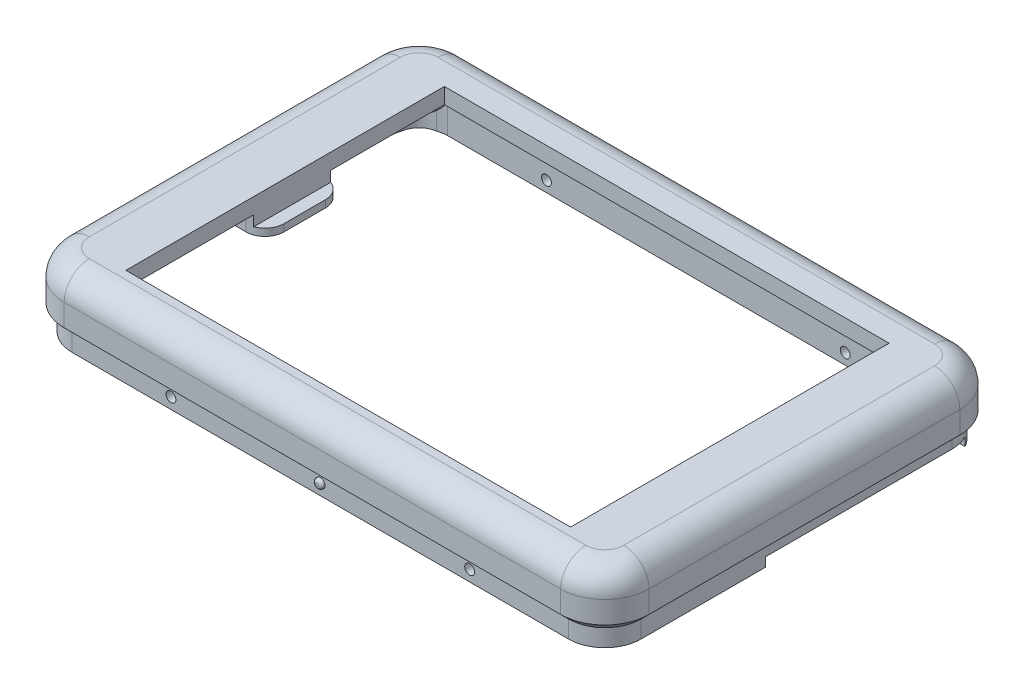
SolidWorks part; units mm, degrees
ref_plane "Front Plane" through (0, 0, 0) normal (0, 0, 1) x (1, 0, 0)
ref_plane "Top Plane" through (0, 0, 0) normal (0, 1, 0) x (1, 0, 0)
ref_plane "Right Plane" through (0, 0, 0) normal (1, 0, 0) x (0, 0, -1)
sketch "Sketch1" plane through (0, 0, 0) normal (0, 1, 0) x (1, 0, 0)
  line L0 (46.3567, -24.641) -> (46.3567, 24.641)
  line L1 (39.3567, 31.641) -> (-39.3567, 31.641)
  line L2 (-46.3567, 24.641) -> (-46.3567, -24.641)
  line L3 (-39.3567, -31.641) -> (39.3567, -31.641)
  arc A0 (46.3567, 24.641) -> (39.3567, 31.641) centre (39.3567, 24.641) ccw
  arc A1 (-39.3567, 31.641) -> (-46.3567, 24.641) centre (-39.3567, 24.641) ccw
  arc A2 (-46.3567, -24.641) -> (-39.3567, -31.641) centre (-39.3567, -24.641) ccw
  arc A3 (39.3567, -31.641) -> (46.3567, -24.641) centre (39.3567, -24.641) ccw
extrude "Boss-Extrude1" add sketch "Sketch1" along normal blind 4.5
shell "Shell1" thickness 2.5 removed face at (0, 0, 0)
sketch "Sketch2" plane through (0, 4.5, 0) normal (0, 1, 0) x (1, 0, 0)
  line L0 (39.3567, 31.641) -> (-39.3567, 31.641) construction
  line L1 (-34.8567, 24.141) -> (35.6433, 24.141)
  line L2 (-34.8567, 24.141) -> (-34.8567, -26.359)
  line L3 (-34.8567, -26.359) -> (35.6433, -26.359)
  line L4 (35.6433, 24.141) -> (35.6433, -26.359)
  line L6 (-43.8567, 24.641) -> (-43.8567, -24.641) construction
  dimension "D1" = 70.5
  dimension "D2" = 50.5
  dimension "D3" = 7.5
  dimension "D4" = 9
extrude "Cut-Extrude1" cut sketch "Sketch2" against normal blind 6
fillet "Fillet1" radius 2 8 edges at (42.5387, 2, 27.823) (0, 2, 29.141) (-42.5387, 2, 27.823) (-43.8567, 2, 0) (-42.5387, 2, -27.823) (0, 2, -29.141) (42.5387, 2, -27.823) (43.8567, 2, 0)
fillet "Fillet2" radius 4 8 edges at (-44.3064, 4.5, 29.5908) (-46.3567, 4.5, 0) (-44.3064, 4.5, -29.5908) (0, 4.5, -31.641) (44.3064, 4.5, -29.5908) (46.3567, 4.5, 0) (44.3064, 4.5, 29.5908) (0, 4.5, 31.641)
sketch "Sketch3" plane through (0, 2, 0) normal (0, -1, 0) x (1, 0, 0)
  circle A0 centre (-40.3931, 23.336) radius 1.25
  circle A1 centre (-40.3931, 23.336) radius 3.25
  circle A2 centre (-40.3931, -25.664) radius 1.25
  circle A3 centre (-40.3931, -25.664) radius 3.25
  circle A4 centre (37.6385, -25.664) radius 1.25
  circle A5 centre (37.6385, -25.664) radius 3.25
  circle A6 centre (37.6385, 23.336) radius 1.25
  circle A7 centre (37.6385, 23.336) radius 3.25
  dimension "D1" = 2
  dimension "D2" = 2
  dimension "D3" = 2
  dimension "D4" = 2
extrude "Boss-Extrude2" add sketch "Sketch3" along normal blind 2.5
sketch "Sketch4" plane through (0, 0, 0) normal (0, -1, 0) x (1, 0, 0)
  line L0 (39.3567, 29.141) -> (-39.3567, 29.141)
  line L1 (-43.8567, 24.641) -> (-43.8567, -24.641)
  line L2 (-39.3567, -29.141) -> (39.3567, -29.141)
  line L3 (43.8567, -24.641) -> (43.8567, 24.641)
  line L4 (39.3567, 31.641) -> (-39.3567, 31.641)
  line L5 (-46.3567, 24.641) -> (-46.3567, -24.641)
  line L6 (-39.3567, -31.641) -> (39.3567, -31.641)
  line L7 (46.3567, -24.641) -> (46.3567, 24.641)
  line L8 (39.3567, 31.641) -> (-39.3567, 31.641)
  line L9 (-46.3567, 24.641) -> (-46.3567, -24.641)
  line L10 (-39.3567, -31.641) -> (39.3567, -31.641)
  line L11 (46.3567, -24.641) -> (46.3567, 24.641)
  arc A0 (-39.3567, 29.141) -> (-43.8567, 24.641) centre (-39.3567, 24.641) ccw
  arc A1 (-43.8567, -24.641) -> (-39.3567, -29.141) centre (-39.3567, -24.641) ccw
  arc A2 (39.3567, -29.141) -> (43.8567, -24.641) centre (39.3567, -24.641) ccw
  arc A3 (43.8567, 24.641) -> (39.3567, 29.141) centre (39.3567, 24.641) ccw
  arc A4 (46.3567, 24.641) -> (39.3567, 31.641) centre (39.3567, 24.641) ccw
  arc A5 (-39.3567, 31.641) -> (-46.3567, 24.641) centre (-39.3567, 24.641) ccw
  arc A6 (-46.3567, -24.641) -> (-39.3567, -31.641) centre (-39.3567, -24.641) ccw
  arc A7 (39.3567, -31.641) -> (46.3567, -24.641) centre (39.3567, -24.641) ccw
  arc A8 (46.3567, 24.641) -> (39.3567, 31.641) centre (39.3567, 24.641) ccw
  arc A9 (-39.3567, 31.641) -> (-46.3567, 24.641) centre (-39.3567, 24.641) ccw
  arc A10 (-46.3567, -24.641) -> (-39.3567, -31.641) centre (-39.3567, -24.641) ccw
  arc A11 (39.3567, -31.641) -> (46.3567, -24.641) centre (39.3567, -24.641) ccw
  dimension "D1" = 0
  dimension "D2" = 2.5
extrude "Boss-Extrude3" add sketch "Sketch4" along normal blind 3
sketch "Sketch5" plane through (-34.8567, 0, 0) normal (1, 0, 0) x (0, 0, -1)
  line L1 (-6.2748, 0.3532) -> (6.2927, 0.3532)
  line L2 (-6.2748, 0.3532) -> (-6.2748, 2)
  line L3 (-6.2748, 2) -> (6.2927, 2)
  line L4 (6.2927, 0.3532) -> (6.2927, 2)
extrude "Boss-Extrude4" add sketch "Sketch5" against normal blind 4
sketch "Sketch6" plane through (0, 0, 6.2748) normal (0, 0, 1) x (1, 0, 0)
  line L0 (-34.8567, 0.3532) -> (-32.8849, 0.3532)
  line L1 (-32.8849, 0.3532) -> (-32.8849, -0.7856)
  line L2 (-32.8849, -0.7856) -> (-38.3084, -0.7856)
  line L3 (-38.3084, -0.7856) -> (-38.8567, 0.3532)
  line L4 (-38.8567, 0.3532) -> (-34.8567, 0.3532)
extrude "Boss-Extrude5" add sketch "Sketch6" against normal up to surface (12.5674 mm away) up to face at (-36.8567, 1.1766, -6.2927)
fillet "Fillet4" radius 3 2 edges at (-32.8849, -0.2162, -6.2927) (-32.8849, -0.2162, 6.2748)
sketch "Sketch8" plane through (0, 4.5, 0) normal (0, 1, 0) x (1, 0, 0)
  line L1 (-34.8567, 24.141) -> (35.6433, 24.141)
  line L2 (-34.8567, 24.141) -> (-34.8567, -26.359)
  line L3 (-34.8567, -26.359) -> (35.6433, -26.359)
  line L4 (35.6433, 24.141) -> (35.6433, -26.359)
extrude "Cut-Extrude2" cut sketch "Sketch8" against normal blind 4
sketch "Sketch10" plane through (0, -3, 0) normal (0, -1, 0) x (1, 0, 0)
  line L4 (-39.3567, -29.141) -> (39.3567, -29.141) construction
  line L5 (43.8567, -24.641) -> (43.8567, 24.641) construction
  line L6 (39.3567, 29.141) -> (-39.3567, 29.141) construction
  line L7 (-43.8567, 24.641) -> (-43.8567, -24.641) construction
  line L8 (-39.3567, -29.141) -> (39.3567, -29.141)
  line L9 (43.8567, -24.641) -> (43.8567, 24.641)
  line L10 (39.3567, 29.141) -> (-39.3567, 29.141)
  line L11 (-43.8567, 24.641) -> (-43.8567, -24.641)
  line L12 (-39.3567, -30.391) -> (39.3567, -30.391)
  line L13 (45.1067, -24.641) -> (45.1067, 24.641)
  line L14 (39.3567, 30.391) -> (-39.3567, 30.391)
  line L15 (-45.1067, 24.641) -> (-45.1067, -24.641)
  arc A4 (39.3567, -29.141) -> (43.8567, -24.641) centre (39.3567, -24.641) ccw construction
  arc A5 (43.8567, 24.641) -> (39.3567, 29.141) centre (39.3567, 24.641) ccw construction
  arc A6 (-39.3567, 29.141) -> (-43.8567, 24.641) centre (-39.3567, 24.641) ccw construction
  arc A7 (-43.8567, -24.641) -> (-39.3567, -29.141) centre (-39.3567, -24.641) ccw construction
  arc A8 (39.3567, -29.141) -> (43.8567, -24.641) centre (39.3567, -24.641) ccw
  arc A9 (43.8567, 24.641) -> (39.3567, 29.141) centre (39.3567, 24.641) ccw
  arc A10 (-39.3567, 29.141) -> (-43.8567, 24.641) centre (-39.3567, 24.641) ccw
  arc A11 (-43.8567, -24.641) -> (-39.3567, -29.141) centre (-39.3567, -24.641) ccw
  arc A12 (39.3567, -30.391) -> (45.1067, -24.641) centre (39.3567, -24.641) ccw
  arc A13 (45.1067, 24.641) -> (39.3567, 30.391) centre (39.3567, 24.641) ccw
  arc A14 (-39.3567, 30.391) -> (-45.1067, 24.641) centre (-39.3567, 24.641) ccw
  arc A15 (-45.1067, -24.641) -> (-39.3567, -30.391) centre (-39.3567, -24.641) ccw
  dimension "D1" = 1.25
extrude "Boss-Extrude6" add sketch "Sketch10" along normal blind 4
chamfer "Chamfer1" distance 1.25 angle 45 8 edges at (0, -3, 30.391) (-43.4226, -3, 28.7069) (43.4226, -3, 28.7069) (-45.1067, -3, 0) (45.1067, -3, 0) (-43.4226, -3, -28.7069) (43.4226, -3, -28.7069) (0, -3, -30.391)
sketch "Sketch11" plane through (0, 4.5, 0) normal (0, 1, 0) x (1, 0, 0)
  line L0 (35.6433, 24.141) -> (-34.8567, 24.141) construction
  line L1 (20.156, 24.141) -> (35.6433, 24.141)
  line L2 (20.156, 24.141) -> (20.156, -26.359)
  line L3 (20.156, -26.359) -> (35.6433, -26.359)
  line L4 (35.6433, 24.141) -> (35.6433, -26.359)
extrude "Cut-Extrude3" cut sketch "Sketch11" against normal blind 24
sketch "Sketch12" plane through (0, -7, 0) normal (0, -1, 0) x (1, 0, 0)
  line L1 (-39.9799, -25.3582) -> (-48.5649, -25.3582)
  line L2 (-39.9799, -25.3582) -> (-39.9799, -33.6082)
  line L3 (-39.9799, -33.6082) -> (-48.5649, -33.6082)
  line L4 (-48.5649, -25.3582) -> (-48.5649, -33.6082)
sketch "Sketch13" plane through (0, -7, 0) normal (0, -1, 0) x (1, 0, 0)
  circle A0 centre (-40.3931, -25.664) radius 3.25
extrude "Cut-Extrude4" cut sketch "Sketch13" against normal up to surface (6.5 mm away) up to face at (-40.3931, -0.5, -26.914)
sketch "Sketch14" plane through (0, 0, -30.391) normal (0, 0, -1) x (-1, 0, 0)
  circle A0 centre (0, -5.25) radius 0.75
extrude "Boss-Extrude7" add sketch "Sketch14" along normal blind 0.5
fillet "Fillet5" radius 0.5 1 edges at (-0.75, -5.25, -30.891)
sketch "Sketch15" plane through (0, 0, 30.391) normal (0, 0, 1) x (1, 0, 0)
  circle A0 centre (0, -5.25) radius 0.75
extrude "Boss-Extrude8" add sketch "Sketch15" along normal blind 0.5
fillet "Fillet6" radius 0.5 1 edges at (0.75, -5.25, 30.891)
sketch "Sketch16" plane through (45.1067, 0, 0) normal (1, 0, 0) x (0, 0, -1)
  line L1 (-4.8925, -5.5711) -> (27.4665, -5.5711)
  line L2 (-4.8925, -5.5711) -> (-4.8925, -7.3216)
  line L3 (-4.8925, -7.3216) -> (27.4665, -7.3216)
  line L4 (27.4665, -5.5711) -> (27.4665, -7.3216)
extrude "Cut-Extrude5" cut sketch "Sketch16" against normal blind 20.5
sketch "Sketch17" plane through (0, 0, -30.391) normal (0, 0, -1) x (-1, 0, 0)
  circle A0 centre (23.6797, -5.2689) radius 0.7839
  circle A1 centre (-23.6797, -5.2689) radius 0.7839
extrude "Cut-Extrude6" cut sketch "Sketch17" against normal through all
